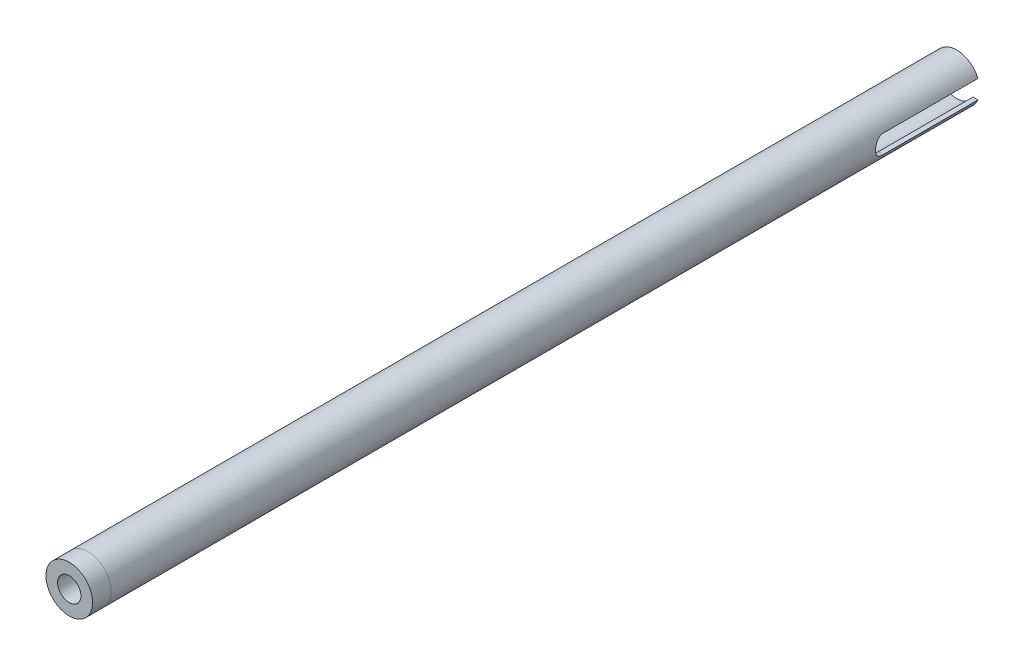
SolidWorks part; units mm, degrees
ref_plane "Front Plane" through (0, 0, 0) normal (0, 0, 1) x (1, 0, 0)
ref_plane "Top Plane" through (0, 0, 0) normal (0, 1, 0) x (1, 0, 0)
ref_plane "Right Plane" through (0, 0, 0) normal (1, 0, 0) x (0, 0, -1)
sketch "Axis" plane through (0, 0, 0) normal (0, 1, 0) x (1, 0, 0)
  line L0 (0, 0) -> (0, 302.3183) construction
  line L1 (0, 0) -> (0, -28.575) construction
  line L2 (0, 302.3183) -> (-7.9375, 302.3183) construction
  line L3 (0, 325.6526) -> (-31.242, 233.8087) construction
  dimension "D1" = 28.575
  dimension "D2" = 7.9375
sketch "Sketch1" plane through (0, 0, 0) normal (0, 0, 1) x (1, 0, 0)
  line L0 (-7.9375, 0) -> (7.9375, 0) construction
  line L1 (-7.2748, 3.175) -> (7.2748, 3.175)
  line L2 (-7.2748, -3.175) -> (7.2748, -3.175)
  circle A0 centre (0, 0) radius 7.9375
  circle A1 centre (0, 0) radius 6.4135
  circle A2 centre (0, 0) radius 3.9688
  dimension "D1" = 15.875
  dimension "D3" = 7.9375
  dimension "D2" = 1.524
  dimension "D4" = 6.35
extrude "Threaded insert 1-1" add sketch "Sketch1" against normal blind 6.35 contours A2 L1 A1 | A1 L1 A0 | A2 L0 A1 L1 | A1 L0 A0 L1 | L0 A1 L2 A0 | L0 A2 L2 A1 | A2 L2 A1 | A1 L2 A0 | L0 A1 L2 A2 | L0 A0 L2 A1 | A0 L0 A1 L1 | A1 L0 A2 L1 region at (4.7887, 1.6543, 0) region at (4.7887, -1.6543, 0) region at (6.9234, 1.6163, 0) region at (6.9234, -1.6163, 0) region at (-4.7887, -1.6543, 0) region at (-4.7887, 1.6543, 0) region at (0, 4.6159, 0) region at (0, -4.6159, 0) region at (0, 6.5666, 0) region at (6.4237, -3.3281, 0) region at (-6.9234, -1.6163, 0) region at (-6.9234, 1.6163, 0)
extrude "Threaded insert 1-2" add sketch "Sketch1<3>" against normal blind 9.525 from surface contours A2 L1 A1 | A2 L0 A1 L1 | L0 A2 L2 A1 | A2 L2 A1 | L0 A1 L2 A2 | A1 L0 A2 L1 region at (4.7887, 1.6543, 0) region at (4.7887, -1.6543, 0) region at (-4.7887, -1.6543, 0) region at (-4.7887, 1.6543, 0) region at (0, 4.6159, 0) region at (0, -4.6159, 0) starting at face at (7.9375, 0, -6.35)
sketch "Sketch1<3>" plane through (0, 0, 0) normal (0, 0, 1) x (1, 0, 0) same geometry as "Sketch1"
extrude "A-arm tube" add sketch "Sketch1<4>" against normal up to vertex (302.3183 mm away) from surface separate body contours A1 L1 A0 | A1 L0 A0 L1 | L0 A1 L2 A0 | A1 L2 A0 | L0 A0 L2 A1 | A0 L0 A1 L1 region at (6.9234, 1.6163, 0) region at (6.9234, -1.6163, 0) region at (0, 6.5666, 0) region at (6.4237, -3.3281, 0) region at (-6.9234, -1.6163, 0) region at (-6.9234, 1.6163, 0) up to point (0, 0, -302.3183) starting at face at (6.4135, 0, -6.35)
sketch "Sketch1<4>" plane through (0, 0, 0) normal (0, 0, 1) x (1, 0, 0) same geometry as "Sketch1"
extrude "Apex slot" cut sketch "Sketch1<5>" along normal blind 35.56 from surface contours A0 L0 A1 L1 | L0 A0 L2 A1 | A1 L0 A0 L1 | L0 A1 L2 A0 region at (6.9234, 1.6163, 0) region at (6.9234, -1.6163, 0) region at (-6.9234, -1.6163, 0) region at (-6.9234, 1.6163, 0) starting at face at (6.4135, 0, -302.3183)
sketch "Sketch1<5>" plane through (0, 0, 0) normal (0, 0, 1) x (1, 0, 0) same geometry as "Sketch1"
fillet "Fillet1" radius 3.175 4 edges at (-6.4237, 3.175, -266.7583) (-6.4237, -3.175, -266.7583) (6.4237, -3.175, -266.7583) (6.4237, 3.175, -266.7583)
equation "\"tube diameter\"= 5 / 8"
equation "\"tube thickness\"= .06"
equation "\"apex thickness\"= .25"
equation "\"tube slot\"= 1.4"
equation "\"D1@Sketch1\"=\"tube diameter\""
equation "\"D2@Sketch1\"=\"tube thickness\""
equation "\"threaded insert hole\"= .3125"
equation "\"D3@Sketch1\"=\"threaded insert hole\""
equation "\"D4@Sketch1\"=\"apex thickness\""
equation "\"D1@Apex slot\" = \"tube slot\""
equation "\"D1@Fillet1\"=\"apex thickness\"/2"
equation "\"D2@Axis\"=\"tube diameter\"/2"
